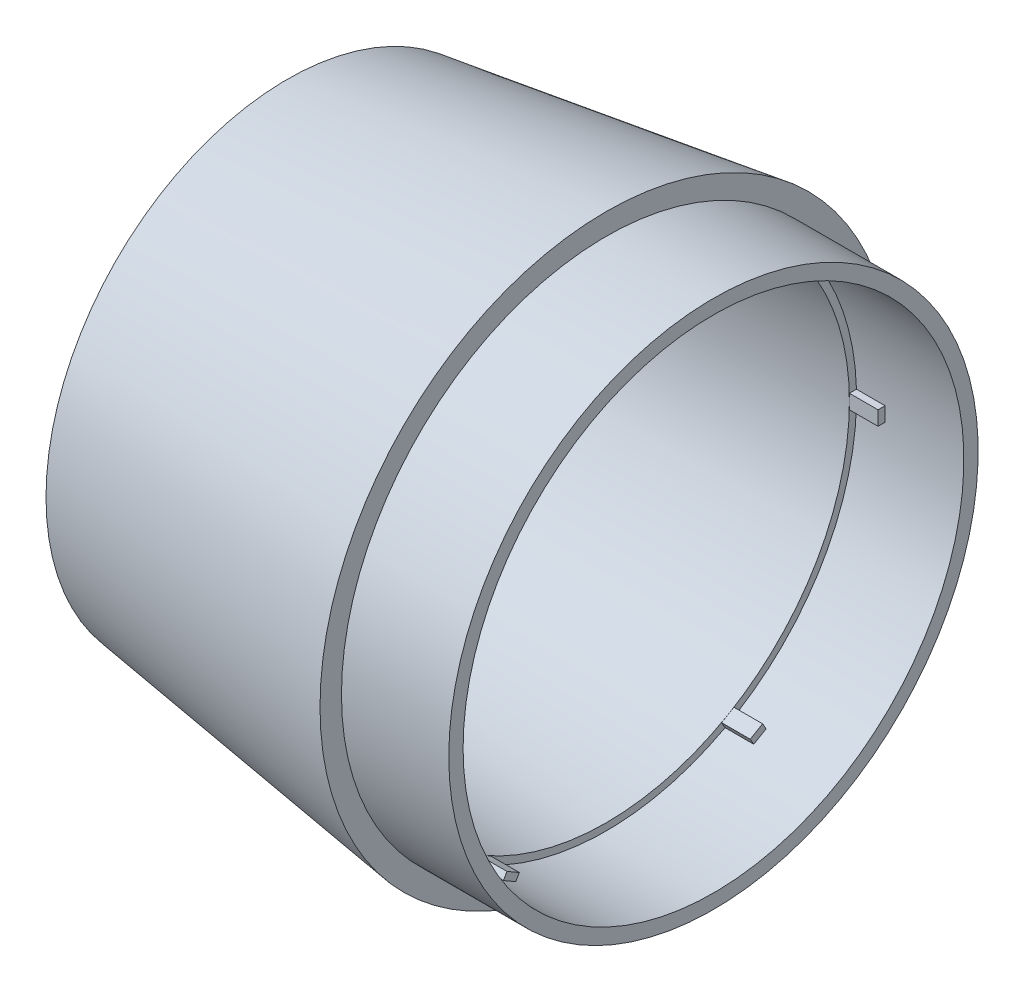
SolidWorks part; units mm, degrees
ref_plane "Ön Düzlem" through (0, 0, 0) normal (0, 0, 1) x (1, 0, 0)
ref_plane "Üst Düzlem" through (0, 0, 0) normal (0, 1, 0) x (1, 0, 0)
ref_plane "Sağ Düzlem" through (0, 0, 0) normal (1, 0, 0) x (0, 0, -1)
sketch "Çizim1" plane through (0, 0, 0) normal (0, 0, 1) x (1, 0, 0)
  line L0 (-44.5621, 33.7372) -> (-44.5621, 31.7372)
  line L1 (0, 40) -> (-44.5621, 33.7372)
  line L4 (-33.5551, 31.7372) -> (-44.5621, 31.7372)
  line L6 (15, 35) -> (15, 37)
  line L7 (-44.3163, 0) -> (0, 0)
  line L15 (0, 37) -> (15, 37)
  line L21 (0, 35) -> (15, 35)
  line L22 (0, 35) -> (0, 34)
  line L23 (0, 40) -> (0, 37)
  line L25 (-33.5551, 31.7372) -> (0, 34)
  dimension "D2" = 44.3163
ref_axis "Eksen1" through (0, 0, 0) along (-1, 0, 0)
revolve "Döndür2" add sketch "Çizim1" angle 360 about L7 region at (-15.4457, 35.1752, 0)
sketch "Çizim3" plane through (0, 0, 0) normal (0, 1, 0) x (1, 0, 0)
  line L4 (0, -35) -> (4, -35)
  line L6 (4, -35) -> (4, -34)
  line L7 (4, -34) -> (0, -34)
  line L9 (0, -34) -> (0, -35)
extrude "Yükseklik-Ekstrüzyon1" add sketch "Çizim3" along normal blind 1 and the other way blind 1
pattern_circular "Dairesel Kaplama2" count 6 over 360 about axis through (0, 0, 0) along (-1, 0, 0) of "Yükseklik-Ekstrüzyon1"
